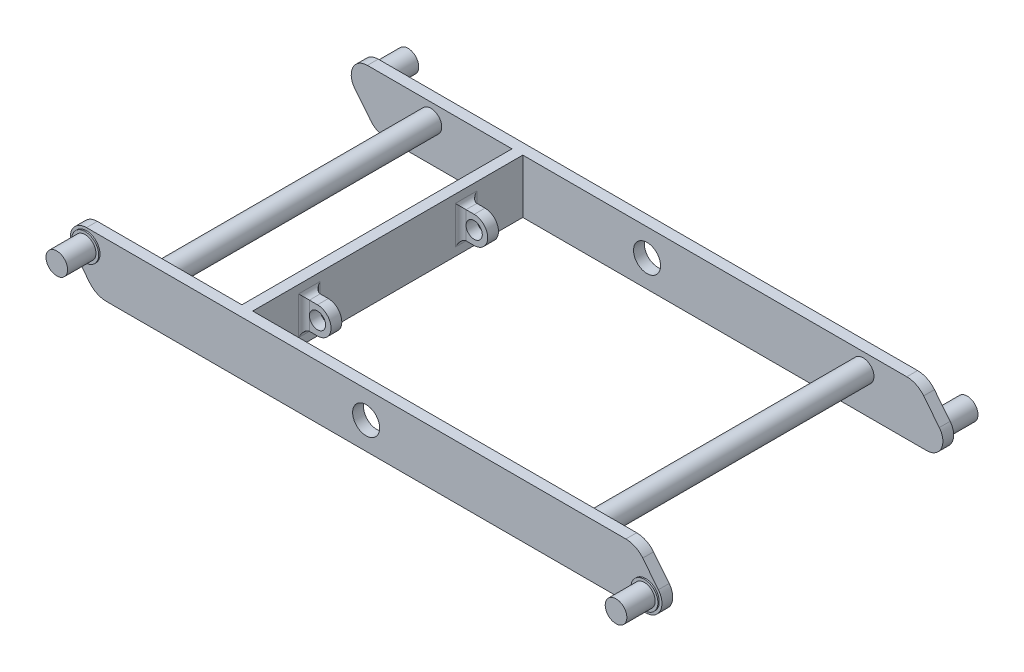
SolidWorks part; units mm, degrees
ref_plane "前基準面" through (0, 0, 0) normal (0, 0, 1) x (1, 0, 0)
ref_plane "上基準面" through (0, 0, 0) normal (0, 1, 0) x (1, 0, 0)
ref_plane "右基準面" through (0, 0, 0) normal (1, 0, 0) x (0, 0, -1)
sketch "草圖1" plane through (0, 0, 0) normal (0, 0, 1) x (1, 0, 0)
  line L0 (-48.0775, -5) -> (51.7581, -5)
  line L5 (54.1007, -0.1259) -> (51.201, 3.4988)
  line L8 (48.0775, 5) -> (-51.7581, 5)
  line L9 (-54.1007, 0.1259) -> (-51.201, -3.4988)
  line L10 (0, 15.1518) -> (0, 0) construction
  line L11 (0, 0) -> (14.8565, 0) construction
  arc A6 (51.7581, -5) -> (54.1007, -0.1259) centre (51.7581, -2) ccw
  arc A7 (-51.7581, 5) -> (-54.1007, 0.1259) centre (-51.7581, 2) ccw
  arc A8 (51.201, 3.4988) -> (48.0775, 5) centre (48.0775, 1) ccw
  arc A9 (-48.0775, -5) -> (-51.201, -3.4988) centre (-48.0775, -1) cw
  point P10 (58, -5)
  point P14 (-58, 5)
  point P18 (50, 5)
  point P21 (-50, -5)
  dimension "D1" = 50
  dimension "D3" = 58
  dimension "D7" = 3
  dimension "D8" = 4
  dimension "D2" = 50
  dimension "D4" = 58
  dimension "D5" = 5
  dimension "D6" = 5
extrude "填料-伸長1" add sketch "草圖1" along normal blind 2
sketch "草圖3" plane through (0, 0, 2) normal (0, 0, 1) x (1, 0, 0)
  circle A0 centre (-51.7581, 2) radius 2
  arc A1 (-51.7581, 5) -> (-54.1007, 0.1259) centre (-51.7581, 2) ccw construction
  circle A2 centre (51.7581, -2) radius 2
  arc A4 (51.7581, -5) -> (54.1007, -0.1259) centre (51.7581, -2) ccw construction
  dimension "D1" = 4
  dimension "D2" = 4
extrude "填料-伸長2" add sketch "草圖3" along normal blind 9
sketch "草圖4" plane through (0, 0, 0) normal (0, 0, -1) x (-1, 0, 0)
  line L0 (0, 0) -> (0, 12.2903) construction
  circle A0 centre (-40, 2) radius 2
  circle A1 centre (40, 2) radius 2
  dimension "D1" = 2
  dimension "D2" = 40
  dimension "D3" = 4
extrude "填料-伸長3" add sketch "草圖4" along normal blind 25
sketch "草圖5" plane through (0, 0, 0) normal (0, 0, -1) x (-1, 0, 0)
  circle A0 centre (0, 0) radius 2.5
  dimension "D1" = 5
extrude "除料-伸長2" cut sketch "草圖5" against normal blind 25
sketch "草圖7" plane through (0, 0, 2) normal (0, 0, 1) x (1, 0, 0)
  circle A0 centre (51.7581, -2) radius 2.5
  circle A1 centre (-51.7581, 2) radius 2.5
  arc A2 (-51.7581, 5) -> (-54.1007, 0.1259) centre (-51.7581, 2) ccw construction
  dimension "D1" = 5
  dimension "D2" = 5
extrude "填料-伸長4" add sketch "草圖7" along normal blind 0.25
sketch "草圖8" plane through (0, 0, 0) normal (0, 1, 0) x (1, 0, 0)
  line L0 (49.7581, -11) -> (53.7581, -11) construction
  line L1 (56.8875, -12.735) -> (42.113, -12.735)
  line L2 (56.8875, -12.735) -> (56.8875, -7.5)
  line L3 (56.8875, -7.5) -> (42.113, -7.5)
  line L4 (42.113, -12.735) -> (42.113, -7.5)
  line L5 (-53.7581, -11) -> (-49.7581, -11) construction
  line L6 (-61.3377, -7.5) -> (-40.2525, -7.5)
  line L7 (-61.3377, -7.5) -> (-61.3377, -18.443)
  line L8 (-61.3377, -18.443) -> (-40.2525, -18.443)
  line L9 (-40.2525, -7.5) -> (-40.2525, -18.443)
  dimension "D1" = 3.5
  dimension "D2" = 3.5
extrude "除料-伸長3" cut sketch "草圖8" against normal blind 10 and the other way through all
mirror "鏡射1" about plane through (-40, 2, -25) normal (0, 0, 1) of bodies 108 105
sketch "草圖9" plane through (0, 0, 2) normal (0, 0, 1) x (1, 0, 0)
  line L0 (-25, -5) -> (-25, 5)
  line L1 (-48.0775, -5) -> (51.7581, -5) construction
  line L2 (48.0775, 5) -> (-51.7581, 5) construction
  line L3 (-23, 5) -> (-23, -5)
  line L4 (-23, -5) -> (-25, -5)
  line L5 (-25, 5) -> (-23, 5)
  dimension "D1" = 25
  dimension "D3" = 2
extrude "填料-伸長5" add sketch "草圖9" against normal blind 54
ref_plane "平面1" through (0, 0, -25) normal (0, 0, -1) x (-1, 0, 0)
sketch "草圖10" plane through (0, 0, -25) normal (0, 0, -1) x (-1, 0, 0)
  line L0 (23, 0) -> (17.3899, 0) construction
  line L1 (23, -5) -> (23, 5) construction
  line L2 (23, 2.5) -> (20.5, 2.5)
  line L3 (20.5, -2.5) -> (23, -2.5)
  line L4 (23, -2.5) -> (23, 2.5)
  arc A0 (20.5, 2.5) -> (20.5, -2.5) centre (20.5, 0) ccw
  circle A1 centre (20.5, 0) radius 1.5
  dimension "D3" = 3
  dimension "D1" = 5
  dimension "D2" = 2.5
extrude "填料-伸長6" add sketch "草圖10" along normal blind 2 from offset 13.5
fillet "圓角3" radius 1 4 edges at (-23, -2.5, -39.5) (-23, 0, -40.5) (-23, 0, -38.5) (-23, 2.5, -39.5)
mirror "鏡射5" about plane through (0, 0, -25) normal (0, 0, -1) of "圓角3", "填料-伸長6"
